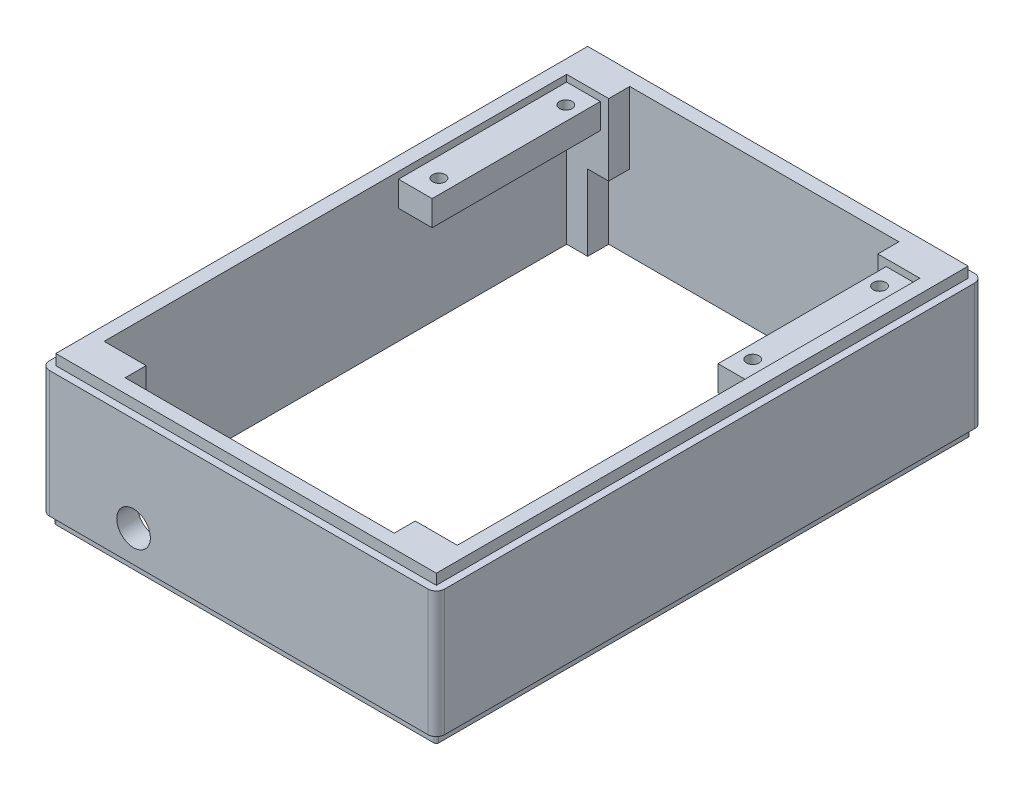
SolidWorks part; units mm, degrees
ref_plane "Front Plane" through (0, 0, 0) normal (0, 0, 1) x (1, 0, 0)
ref_plane "Top Plane" through (0, 0, 0) normal (0, 1, 0) x (1, 0, 0)
ref_plane "Right Plane" through (0, 0, 0) normal (1, 0, 0) x (0, 0, -1)
ref_plane "Plane1" through (0, 0, 0) normal (0, -1, 0) x (1, 0, 0)
sketch "Sketch1" plane through (0, 0, 0) normal (0, -1, 0) x (1, 0, 0)
  line L0 (94, 0) -> (0, 0)
  line L1 (0, 0) -> (0, -130)
  line L2 (0, -130) -> (94, -130)
  line L3 (94, -130) -> (94, 0)
extrude "Boss-Extrude1" add sketch "Sketch1" against normal blind 32.5
sketch "Sketch2" plane through (0, 32.5, 0) normal (0, 1, 0) x (-1, 0, 0)
  line L0 (-1.75, -128.25) -> (-92.25, -128.25)
  line L1 (-92.25, -128.25) -> (-92.25, -1.75)
  line L2 (-92.25, -1.75) -> (-1.75, -1.75)
  line L3 (-1.75, -1.75) -> (-1.75, -128.25)
extrude "Boss-Extrude2" add sketch "Sketch2" along normal blind 2.5
sketch "Sketch3" plane through (0, 35, 0) normal (0, 1, 0) x (-1, 0, 0)
  line L1 (-83, -120) -> (-79, -120)
  line L2 (-79, -120) -> (-79, -125)
  line L3 (-79, -125) -> (-15, -125)
  line L4 (-15, -125) -> (-15, -120)
  line L5 (-15, -120) -> (-5, -120)
  line L6 (-5, -120) -> (-5, -10)
  line L7 (-5, -10) -> (-15, -10)
  line L8 (-15, -10) -> (-15, -5)
  line L9 (-15, -5) -> (-79, -5)
  line L10 (-79, -5) -> (-79, -10)
  line L11 (-79, -10) -> (-89, -10)
  line L12 (-89, -10) -> (-89, -96)
  line L14 (-83, -120) -> (-89, -120)
  line L15 (-89, -120) -> (-89, -96)
extrude "Cut-Extrude1" cut sketch "Sketch3" against normal through all
sketch "Sketch4" plane through (0, 0, -10) normal (0, 0, -1) x (-1, 0, 0)
  line L0 (-15, 0) -> (-10, 0)
  line L1 (-10, 0) -> (-10, 18)
  line L2 (-10, 18) -> (-15, 18)
  line L3 (-15, 18) -> (-15, 0)
extrude "Cut-Extrude2" cut sketch "Sketch4" against normal blind 5
ref_plane "Plane2" through (0, 33.5, 0) normal (0, 1, 0) x (1, 0, 0)
ref_plane "Plane3" through (0, 31.5, 0) normal (0, -1, 0) x (1, 0, 0)
sketch "Sketch9" plane through (0, 0, -10) normal (0, 0, -1) x (-1, 0, 0)
  line L0 (-79, 18) -> (-84, 18)
  line L1 (-84, 18) -> (-84, 0)
  line L2 (-84, 0) -> (-79, 0)
  line L3 (-79, 0) -> (-79, 18)
extrude "Cut-Extrude6" cut sketch "Sketch9" against normal blind 5
sketch "Sketch11" plane through (0, 0, 0) normal (0, -1, 0) x (1, 0, 0)
  line L0 (15, -125) -> (15, -120)
  line L1 (15, -120) -> (10, -120)
  line L2 (10, -120) -> (10, -125)
  line L3 (10, -125) -> (15, -125)
extrude "Cut-Extrude8" cut sketch "Sketch11" against normal blind 18
sketch "Sketch12" plane through (0, 0, -120) normal (0, 0, 1) x (1, 0, 0)
  line L0 (79, 0) -> (84, 0)
  line L1 (84, 0) -> (84, 18)
  line L2 (84, 18) -> (79, 18)
  line L3 (79, 18) -> (79, 0)
extrude "Cut-Extrude9" cut sketch "Sketch12" against normal blind 5
hole_wizard "Ø8.0 (8) Diameter Hole1" positions "Sketch14" profile "Sketch13" hole size "Ø8.0" standard "ANSI Metric"
sketch "Sketch14" plane through (0, 0, -5) normal (0, 0, -1) x (-1, 0, 0)
  point P0 (-22, 10)
sketch "Sketch13" plane through (22, 10, -5) normal (1, 0, 0) x (0, 1, 0)
  line L0 (0, 0) -> (0, 5)
  line L1 (0, 5) -> (4, 5)
  line L2 (4, 5) -> (4, 0)
  line L5 (4, 0) -> (0, 0)
  line L11 (0, -6.35) -> (0, 107.95) construction
  dimension "Thru Hole Dia." = 8
  dimension "Thru Hole Depth" = 5
ref_plane "Plane4" through (0, 29.5, 0) normal (0, -1, 0) x (1, 0, 0)
fillet "Fillet1" radius 2 4 edges at (0, 16.25, -130) (94, 16.25, -130) (0, 16.25, 0) (94, 16.25, 0) tangent propagation no
sketch "Sketch16" plane through (0, 0, 0) normal (0, -1, 0) x (1, 0, 0)
  line L4 (1.5, -2) -> (1.5, -128)
  line L5 (2, -128.5) -> (92, -128.5)
  line L6 (92.5, -128) -> (92.5, -2)
  line L7 (92, -1.5) -> (2, -1.5)
  line L8 (0, -2) -> (0, -128)
  line L9 (2, -130) -> (92, -130)
  line L10 (94, -128) -> (94, -2)
  line L11 (92, 0) -> (2, 0)
  line L12 (0, -2) -> (0, -128)
  line L13 (2, -130) -> (92, -130)
  line L14 (94, -128) -> (94, -2)
  line L15 (92, 0) -> (2, 0)
  arc A4 (1.5, -128) -> (2, -128.5) centre (2, -128) ccw
  arc A5 (92, -128.5) -> (92.5, -128) centre (92, -128) ccw
  arc A6 (92.5, -2) -> (92, -1.5) centre (92, -2) ccw
  arc A7 (2, -1.5) -> (1.5, -2) centre (2, -2) ccw
  arc A8 (0, -128) -> (2, -130) centre (2, -128) ccw
  arc A9 (92, -130) -> (94, -128) centre (92, -128) ccw
  arc A10 (94, -2) -> (92, 0) centre (92, -2) ccw
  arc A11 (2, 0) -> (0, -2) centre (2, -2) ccw
  arc A12 (0, -128) -> (2, -130) centre (2, -128) ccw
  arc A13 (92, -130) -> (94, -128) centre (92, -128) ccw
  arc A14 (94, -2) -> (92, 0) centre (92, -2) ccw
  arc A15 (2, 0) -> (0, -2) centre (2, -2) ccw
  dimension "D1" = 0
  dimension "D2" = 1.5
extrude "Cut-Extrude10" cut sketch "Sketch16" against normal blind 2.5
sketch "Sketch17" plane through (5, 0, 0) normal (1, 0, 0) x (0, 0, -1)
  line L0 (120, 35) -> (10, 35) construction
  line L1 (120, 33.4) -> (80, 33.4)
  line L2 (120, 33.4) -> (120, 27.4)
  line L3 (120, 27.4) -> (80, 27.4)
  line L4 (80, 33.4) -> (80, 27.4)
  line L6 (120, 0) -> (120, 35) construction
  dimension "D1" = 40
  dimension "D2" = 6
  dimension "D3" = 1.6
extrude "Boss-Extrude3" add sketch "Sketch17" along normal blind 8
sketch "Sketch18" plane through (89, 0, 0) normal (-1, 0, 0) x (0, 0, 1)
  line L0 (-10, 35) -> (-120, 35) construction
  line L1 (-120, 27.4) -> (-80, 27.4)
  line L2 (-120, 27.4) -> (-120, 33.4)
  line L3 (-120, 33.4) -> (-80, 33.4)
  line L4 (-80, 27.4) -> (-80, 33.4)
  line L5 (-120, 0) -> (-120, 35) construction
  dimension "D1" = 6
  dimension "D2" = 40
  dimension "D3" = 1.6
extrude "Boss-Extrude4" add sketch "Sketch18" along normal blind 8
sketch "Sketch23" plane through (0, 33.4, 0) normal (0, 1, 0) x (1, 0, 0)
  circle A0 centre (9.6187, 115.175) radius 1.5
  circle A1 centre (9.6187, 85.0125) radius 1.5
  circle A2 centre (84.2312, 115.175) radius 1.5
  circle A3 centre (84.2312, 85.0125) radius 1.5
  dimension "D1" = 3
  dimension "D2" = 3
  dimension "D3" = 3
  dimension "D4" = 3
extrude "Cut-Extrude11" cut sketch "Sketch23" against normal blind 4.4
ref_plane "Plane5" through (0, 0, -5) normal (0, 0, -1) x (-1, 0, 0)
ref_axis "Axis1" through (22, 10, 0) along (0, 0, -1)
ref_point "Point1"
ref_plane "Plane6" through (0, 0, 0) normal (0, 0, 1) x (1, 0, 0)
ref_point "Point2"
